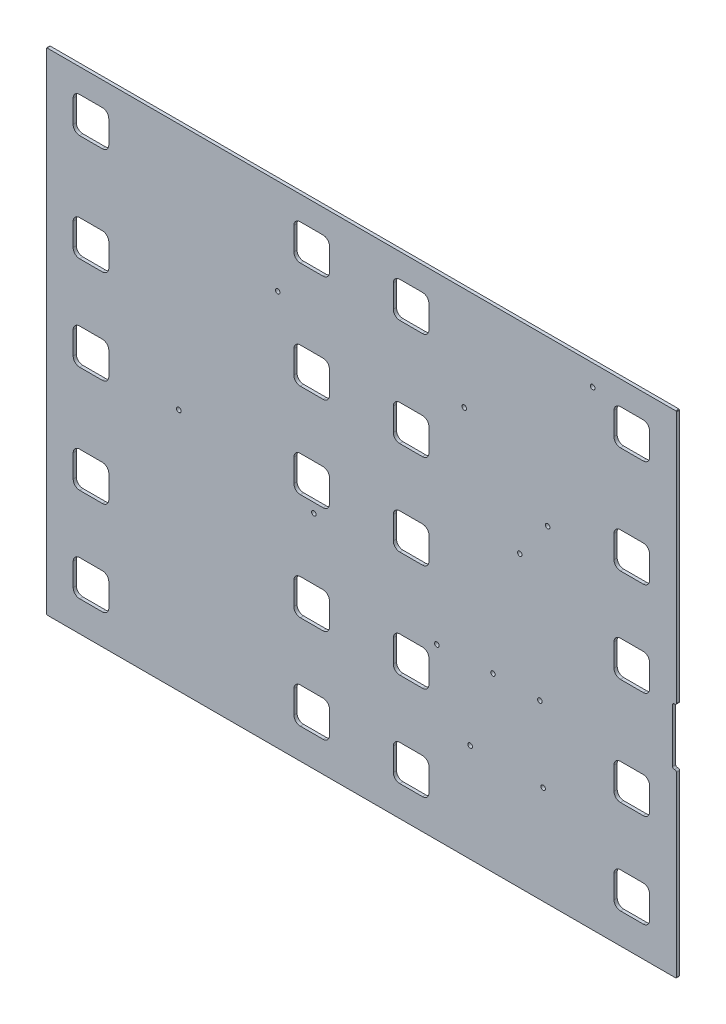
SolidWorks part; units mm, degrees
material "PP Film"
ref_plane "X-Y Datum" through (0, 0, 0) normal (0, 0, 1) x (1, 0, 0)
ref_plane "X-Z Datum" through (0, 0, 0) normal (0, 1, 0) x (1, 0, 0)
ref_plane "Y-Z Datum" through (0, 0, 0) normal (1, 0, 0) x (0, 0, -1)
sketch "Sketch9" plane through (0, 0, 0) normal (0, 0, 1) x (1, 0, 0)
  line L0 (-82.7559, -182.5893) -> (-82.7583, -160.1613) construction
  line L1 (-89.109, -153.8119) -> (-111.537, -153.8143) construction
  line L2 (-117.8863, -160.165) -> (-117.8839, -182.593) construction
  line L3 (-111.5333, -188.9423) -> (-89.1053, -188.9399) construction
  line L4 (476.4425, 172.8027) -> (-143.9348, 172.7375)
  line L12 (-111.5443, -83.8117) -> (-89.1163, -83.8093) construction
  line L13 (-82.767, -77.4587) -> (-82.7693, -55.0307) construction
  line L14 (-89.12, -48.6813) -> (-111.548, -48.6837) construction
  line L15 (-117.8973, -55.0344) -> (-117.895, -77.4624) construction
  line L16 (-82.7877, 120.2549) -> (-82.7901, 142.6829) construction
  line L17 (-89.1408, 149.0323) -> (-111.5688, 149.0299) construction
  line L18 (-117.9181, 142.6792) -> (-117.9157, 120.2512) construction
  line L19 (-111.5651, 113.9019) -> (-89.1371, 113.9043) construction
  line L20 (-111.554, 8.7713) -> (-89.126, 8.7737) construction
  line L21 (-117.9071, 37.5486) -> (-117.9047, 15.1206) construction
  line L22 (-89.1297, 43.9017) -> (-111.5577, 43.8993) construction
  line L23 (-82.7767, 15.1243) -> (-82.7791, 37.5523) construction
  line L24 (-82.7559, -182.5893) -> (-82.7583, -160.1613)
  line L25 (-89.109, -153.8119) -> (-111.537, -153.8143)
  line L26 (-117.8863, -160.165) -> (-117.8839, -182.593)
  line L27 (-111.5333, -188.9423) -> (-89.1053, -188.9399)
  line L28 (-111.5443, -83.8117) -> (-89.1163, -83.8093)
  line L29 (-82.767, -77.4587) -> (-82.7693, -55.0307)
  line L30 (-89.12, -48.6813) -> (-111.548, -48.6837)
  line L31 (-117.8973, -55.0344) -> (-117.895, -77.4624)
  line L32 (-82.7877, 120.2549) -> (-82.7901, 142.6829)
  line L33 (-89.1408, 149.0323) -> (-111.5688, 149.0299)
  line L34 (-117.9181, 142.6792) -> (-117.9157, 120.2512)
  line L35 (-111.5651, 113.9019) -> (-89.1371, 113.9043)
  line L36 (-111.554, 8.7713) -> (-89.126, 8.7737)
  line L37 (-117.9071, 37.5486) -> (-117.9047, 15.1206)
  line L38 (-89.1297, 43.9017) -> (-111.5577, 43.8993)
  line L39 (-82.7767, 15.1243) -> (-82.7791, 37.5523)
  line L40 (-82.7462, -275.1723) -> (-82.7486, -252.7443) construction
  line L41 (-89.0992, -246.3949) -> (-111.5272, -246.3973) construction
  line L42 (-117.8766, -252.748) -> (-117.8742, -275.176) construction
  line L43 (-111.5235, -281.5253) -> (-89.0955, -281.5229) construction
  line L44 (-82.7462, -275.1723) -> (-82.7486, -252.7443)
  line L45 (-89.0992, -246.3949) -> (-111.5272, -246.3973)
  line L46 (-117.8766, -252.748) -> (-117.8742, -275.176)
  line L47 (-111.5235, -281.5253) -> (-89.0955, -281.5229)
  line L195 (476.4425, 172.8027) -> (-143.9348, 172.7375)
  line L254 (-144.3754, 172.2968) -> (-144.3246, -311.0729)
  line L255 (-144.3754, 172.2968) -> (-144.3246, -311.0729)
  line L256 (-143.884, -311.5135) -> (476.4934, -311.4483)
  line L257 (-143.884, -311.5135) -> (476.4934, -311.4483)
  line L258 (476.934, -311.0077) -> (476.8832, 172.3621)
  line L259 (476.934, -311.0077) -> (476.8832, 172.3621)
  arc A0 (-89.1053, -188.9399) -> (-82.7559, -182.5893) centre (-89.1059, -182.5899) ccw construction
  arc A1 (-82.7583, -160.1613) -> (-89.109, -153.8119) centre (-89.1083, -160.1619) ccw construction
  arc A2 (-111.537, -153.8143) -> (-117.8863, -160.165) centre (-111.5363, -160.1643) ccw construction
  arc A3 (-117.8839, -182.593) -> (-111.5333, -188.9423) centre (-111.5339, -182.5923) ccw construction
  arc A4 (-89.1163, -83.8093) -> (-82.767, -77.4587) centre (-89.117, -77.4593) ccw construction
  arc A5 (-82.7693, -55.0307) -> (-89.12, -48.6813) centre (-89.1193, -55.0313) ccw construction
  arc A6 (-111.548, -48.6837) -> (-117.8973, -55.0344) centre (-111.5473, -55.0337) ccw construction
  arc A7 (-117.895, -77.4624) -> (-111.5443, -83.8117) centre (-111.545, -77.4617) ccw construction
  arc A8 (-89.1371, 113.9043) -> (-82.7877, 120.2549) centre (-89.1377, 120.2543) ccw construction
  arc A9 (-82.7901, 142.6829) -> (-89.1408, 149.0323) centre (-89.1401, 142.6823) ccw construction
  arc A10 (-111.5688, 149.0299) -> (-117.9181, 142.6792) centre (-111.5681, 142.6799) ccw construction
  arc A11 (-117.9157, 120.2512) -> (-111.5651, 113.9019) centre (-111.5657, 120.2519) ccw construction
  arc A12 (-82.7791, 37.5523) -> (-89.1297, 43.9017) centre (-89.1291, 37.5517) ccw construction
  arc A13 (-89.126, 8.7737) -> (-82.7767, 15.1243) centre (-89.1267, 15.1237) ccw construction
  arc A14 (-117.9047, 15.1206) -> (-111.554, 8.7713) centre (-111.5547, 15.1213) ccw construction
  arc A15 (-111.5577, 43.8993) -> (-117.9071, 37.5486) centre (-111.5571, 37.5493) ccw construction
  arc A16 (-89.1053, -188.9399) -> (-82.7559, -182.5893) centre (-89.1059, -182.5899) ccw
  arc A17 (-82.7583, -160.1613) -> (-89.109, -153.8119) centre (-89.1083, -160.1619) ccw
  arc A18 (-111.537, -153.8143) -> (-117.8863, -160.165) centre (-111.5363, -160.1643) ccw
  arc A19 (-117.8839, -182.593) -> (-111.5333, -188.9423) centre (-111.5339, -182.5923) ccw
  arc A20 (-89.1163, -83.8093) -> (-82.767, -77.4587) centre (-89.117, -77.4593) ccw
  arc A21 (-82.7693, -55.0307) -> (-89.12, -48.6813) centre (-89.1193, -55.0313) ccw
  arc A22 (-111.548, -48.6837) -> (-117.8973, -55.0344) centre (-111.5473, -55.0337) ccw
  arc A23 (-117.895, -77.4624) -> (-111.5443, -83.8117) centre (-111.545, -77.4617) ccw
  arc A24 (-89.1371, 113.9043) -> (-82.7877, 120.2549) centre (-89.1377, 120.2543) ccw
  arc A25 (-82.7901, 142.6829) -> (-89.1408, 149.0323) centre (-89.1401, 142.6823) ccw
  arc A26 (-111.5688, 149.0299) -> (-117.9181, 142.6792) centre (-111.5681, 142.6799) ccw
  arc A27 (-117.9157, 120.2512) -> (-111.5651, 113.9019) centre (-111.5657, 120.2519) ccw
  arc A28 (-82.7791, 37.5523) -> (-89.1297, 43.9017) centre (-89.1291, 37.5517) ccw
  arc A29 (-89.126, 8.7737) -> (-82.7767, 15.1243) centre (-89.1267, 15.1237) ccw
  arc A30 (-117.9047, 15.1206) -> (-111.554, 8.7713) centre (-111.5547, 15.1213) ccw
  arc A31 (-111.5577, 43.8993) -> (-117.9071, 37.5486) centre (-111.5571, 37.5493) ccw
  arc A32 (-89.0955, -281.5229) -> (-82.7462, -275.1723) centre (-89.0962, -275.1729) ccw construction
  arc A33 (-111.5272, -246.3973) -> (-117.8766, -252.748) centre (-111.5266, -252.7473) ccw construction
  arc A34 (-117.8742, -275.176) -> (-111.5235, -281.5253) centre (-111.5242, -275.1753) ccw construction
  arc A35 (-89.0955, -281.5229) -> (-82.7462, -275.1723) centre (-89.0962, -275.1729) ccw
  arc A36 (-111.5272, -246.3973) -> (-117.8766, -252.748) centre (-111.5266, -252.7473) ccw
  arc A37 (-117.8742, -275.176) -> (-111.5235, -281.5253) centre (-111.5242, -275.1753) ccw
  arc A38 (-82.7486, -252.7443) -> (-89.0992, -246.3949) centre (-89.0986, -252.7449) ccw construction
  arc A39 (-82.7486, -252.7443) -> (-89.0992, -246.3949) centre (-89.0986, -252.7449) ccw
  arc A72 (-143.884, -311.5135) -> (-144.3246, -311.0729) centre (-145.2049, -312.394) ccw
  arc A120 (-143.884, -311.5135) -> (-144.3246, -311.0729) centre (-145.2049, -312.394) ccw
  arc A150 (476.934, -311.0077) -> (476.4934, -311.4483) centre (477.8145, -312.3286) ccw
  arc A151 (476.934, -311.0077) -> (476.4934, -311.4483) centre (477.8145, -312.3286) ccw
  arc A152 (476.4425, 172.8027) -> (476.8832, 172.3621) centre (477.7634, 173.6832) ccw
  arc A153 (476.4425, 172.8027) -> (476.8832, 172.3621) centre (477.7634, 173.6832) ccw
  arc A154 (-144.3754, 172.2968) -> (-143.9348, 172.7375) centre (-145.2559, 173.6178) ccw
  arc A156 (-144.3754, 172.2968) -> (-143.9348, 172.7375) centre (-145.2559, 173.6178) ccw
  dimension "D1" = 0
extrude "Boss-Extrude2" add sketch "Sketch9" along normal blind 3.175 contours L255 L257 L195 A39 L44 A35 L47 A37 L46 A36 L45 A31 L38 A28 L39 A29 L36 A30 L37 A27 L34 A26 L33 A25 L32 A24 L35 A23 L31 A22 L30 A21 L29 A20 L28 A19 L26 A18 L25 A17 L24 A16 L27 | L44 A39 L45 A36 L46 A37 L47 A35 | L26 A19 L27 A16 L24 A17 L25 A18 | L38 A31 L37 A30 L36 A29 L39 A28 | L34 A27 L35 A24 L32 A25 L33 A26 | L31 A23 L28 A20 L29 A21 L30 A22 region at (171.7018, -69.3676, 0) region at (-100.3211, -171.3771, 0) region at (-100.3322, -66.2465, 0) region at (-100.3529, 131.4671, 0) region at (-100.3419, 26.3365, 0) region at (-100.3114, -263.9601, 0)
sketch "Sketch10" plane through (0, 0, 3.175) normal (0, 0, 1) x (1, 0, 0)
  line L9 (476.8831, 172.8027) -> (-144.3755, 172.7375)
  line L10 (-144.3755, 172.7375) -> (-144.3246, -311.5135)
  line L11 (-144.3246, -311.5135) -> (476.934, -311.4483)
  line L12 (-117.8863, -160.165) -> (-117.8839, -182.593)
  line L13 (-111.5333, -188.9423) -> (-89.1053, -188.9399)
  line L14 (-82.7559, -182.5893) -> (-82.7583, -160.1613)
  line L15 (-89.109, -153.8119) -> (-111.537, -153.8143)
  line L16 (-117.8863, -160.165) -> (-117.8839, -182.593)
  line L17 (-111.5333, -188.9423) -> (-89.1053, -188.9399)
  line L18 (-82.7559, -182.5893) -> (-82.7583, -160.1613)
  line L19 (-89.109, -153.8119) -> (-111.537, -153.8143)
  line L20 (-117.8766, -252.748) -> (-117.8742, -275.176)
  line L21 (-89.0992, -246.3949) -> (-111.5272, -246.3973)
  line L22 (-82.7462, -275.1723) -> (-82.7486, -252.7443)
  line L23 (-111.5235, -281.5253) -> (-89.0955, -281.5229)
  line L24 (-117.8766, -252.748) -> (-117.8742, -275.176)
  line L25 (-89.0992, -246.3949) -> (-111.5272, -246.3973)
  line L26 (-82.7462, -275.1723) -> (-82.7486, -252.7443)
  line L27 (-111.5235, -281.5253) -> (-89.0955, -281.5229)
  line L28 (-89.12, -48.6813) -> (-111.548, -48.6837)
  line L29 (-117.8973, -55.0344) -> (-117.895, -77.4624)
  line L30 (-111.5443, -83.8117) -> (-89.1163, -83.8093)
  line L31 (-82.767, -77.4587) -> (-82.7693, -55.0307)
  line L32 (-89.12, -48.6813) -> (-111.548, -48.6837)
  line L33 (-117.8973, -55.0344) -> (-117.895, -77.4624)
  line L34 (-111.5443, -83.8117) -> (-89.1163, -83.8093)
  line L35 (-82.767, -77.4587) -> (-82.7693, -55.0307)
  line L36 (-82.7877, 120.2549) -> (-82.7901, 142.6829)
  line L37 (-111.5651, 113.9019) -> (-89.1371, 113.9043)
  line L38 (-117.9181, 142.6792) -> (-117.9157, 120.2512)
  line L39 (-89.1408, 149.0323) -> (-111.5688, 149.0299)
  line L40 (-82.7877, 120.2549) -> (-82.7901, 142.6829)
  line L41 (-111.5651, 113.9019) -> (-89.1371, 113.9043)
  line L42 (-117.9181, 142.6792) -> (-117.9157, 120.2512)
  line L43 (-89.1408, 149.0323) -> (-111.5688, 149.0299)
  line L44 (-111.554, 8.7713) -> (-89.126, 8.7737)
  line L45 (-82.7767, 15.1243) -> (-82.7791, 37.5523)
  line L46 (-89.1297, 43.9017) -> (-111.5577, 43.8993)
  line L47 (-117.9071, 37.5486) -> (-117.9047, 15.1206)
  line L48 (-111.554, 8.7713) -> (-89.126, 8.7737)
  line L49 (-82.7767, 15.1243) -> (-82.7791, 37.5523)
  line L50 (-89.1297, 43.9017) -> (-111.5577, 43.8993)
  line L51 (-117.9071, 37.5486) -> (-117.9047, 15.1206)
  line L53 (476.934, -311.4483) -> (476.8831, 172.8027)
  arc A4 (-117.8839, -182.593) -> (-111.5333, -188.9423) centre (-111.5339, -182.5923) ccw
  arc A5 (-89.1053, -188.9399) -> (-82.7559, -182.5893) centre (-89.1059, -182.5899) ccw
  arc A6 (-82.7583, -160.1613) -> (-89.109, -153.8119) centre (-89.1083, -160.1619) ccw
  arc A7 (-111.537, -153.8143) -> (-117.8863, -160.165) centre (-111.5363, -160.1643) ccw
  arc A8 (-117.8839, -182.593) -> (-111.5333, -188.9423) centre (-111.5339, -182.5923) ccw
  arc A9 (-89.1053, -188.9399) -> (-82.7559, -182.5893) centre (-89.1059, -182.5899) ccw
  arc A10 (-82.7583, -160.1613) -> (-89.109, -153.8119) centre (-89.1083, -160.1619) ccw
  arc A11 (-111.537, -153.8143) -> (-117.8863, -160.165) centre (-111.5363, -160.1643) ccw
  arc A12 (-111.5272, -246.3973) -> (-117.8766, -252.748) centre (-111.5266, -252.7473) ccw
  arc A13 (-82.7486, -252.7443) -> (-89.0992, -246.3949) centre (-89.0986, -252.7449) ccw
  arc A14 (-89.0955, -281.5229) -> (-82.7462, -275.1723) centre (-89.0962, -275.1729) ccw
  arc A15 (-117.8742, -275.176) -> (-111.5235, -281.5253) centre (-111.5242, -275.1753) ccw
  arc A16 (-111.5272, -246.3973) -> (-117.8766, -252.748) centre (-111.5266, -252.7473) ccw
  arc A17 (-82.7486, -252.7443) -> (-89.0992, -246.3949) centre (-89.0986, -252.7449) ccw
  arc A18 (-89.0955, -281.5229) -> (-82.7462, -275.1723) centre (-89.0962, -275.1729) ccw
  arc A19 (-117.8742, -275.176) -> (-111.5235, -281.5253) centre (-111.5242, -275.1753) ccw
  arc A20 (-111.548, -48.6837) -> (-117.8973, -55.0344) centre (-111.5473, -55.0337) ccw
  arc A21 (-117.895, -77.4624) -> (-111.5443, -83.8117) centre (-111.545, -77.4617) ccw
  arc A22 (-89.1163, -83.8093) -> (-82.767, -77.4587) centre (-89.117, -77.4593) ccw
  arc A23 (-82.7693, -55.0307) -> (-89.12, -48.6813) centre (-89.1193, -55.0313) ccw
  arc A24 (-111.548, -48.6837) -> (-117.8973, -55.0344) centre (-111.5473, -55.0337) ccw
  arc A25 (-117.895, -77.4624) -> (-111.5443, -83.8117) centre (-111.545, -77.4617) ccw
  arc A26 (-89.1163, -83.8093) -> (-82.767, -77.4587) centre (-89.117, -77.4593) ccw
  arc A27 (-82.7693, -55.0307) -> (-89.12, -48.6813) centre (-89.1193, -55.0313) ccw
  arc A28 (-89.1371, 113.9043) -> (-82.7877, 120.2549) centre (-89.1377, 120.2543) ccw
  arc A29 (-117.9157, 120.2512) -> (-111.5651, 113.9019) centre (-111.5657, 120.2519) ccw
  arc A30 (-111.5688, 149.0299) -> (-117.9181, 142.6792) centre (-111.5681, 142.6799) ccw
  arc A31 (-82.7901, 142.6829) -> (-89.1408, 149.0323) centre (-89.1401, 142.6823) ccw
  arc A32 (-89.1371, 113.9043) -> (-82.7877, 120.2549) centre (-89.1377, 120.2543) ccw
  arc A33 (-117.9157, 120.2512) -> (-111.5651, 113.9019) centre (-111.5657, 120.2519) ccw
  arc A34 (-111.5688, 149.0299) -> (-117.9181, 142.6792) centre (-111.5681, 142.6799) ccw
  arc A35 (-82.7901, 142.6829) -> (-89.1408, 149.0323) centre (-89.1401, 142.6823) ccw
  arc A36 (-89.126, 8.7737) -> (-82.7767, 15.1243) centre (-89.1267, 15.1237) ccw
  arc A37 (-82.7791, 37.5523) -> (-89.1297, 43.9017) centre (-89.1291, 37.5517) ccw
  arc A38 (-111.5577, 43.8993) -> (-117.9071, 37.5486) centre (-111.5571, 37.5493) ccw
  arc A39 (-117.9047, 15.1206) -> (-111.554, 8.7713) centre (-111.5547, 15.1213) ccw
  arc A40 (-89.126, 8.7737) -> (-82.7767, 15.1243) centre (-89.1267, 15.1237) ccw
  arc A41 (-82.7791, 37.5523) -> (-89.1297, 43.9017) centre (-89.1291, 37.5517) ccw
  arc A42 (-111.5577, 43.8993) -> (-117.9071, 37.5486) centre (-111.5571, 37.5493) ccw
  arc A43 (-117.9047, 15.1206) -> (-111.554, 8.7713) centre (-111.5547, 15.1213) ccw
  dimension "D2" = 0
  dimension "D3" = 0
  dimension "D4" = 0
  dimension "D5" = 0
  dimension "D6" = 0
extrude "Cut-Extrude6" cut sketch "Sketch10" against normal through all contours L40 A35 L43 A34 L42 A33 L41 A32 | L51 A43 L48 A40 L49 A41 L50 A42 | L35 A27 L32 A24 L33 A25 L34 A26 | L19 A11 L16 A8 L17 A9 L18 A10 | L24 A19 L27 A18 L26 A17 L25 A16 region at (-100.3211, -171.3771, 3.175) region at (-100.3114, -263.9601, 3.175) region at (-100.3322, -66.2465, 3.175) region at (-100.3529, 131.4671, 3.175) region at (-100.3419, 26.3365, 3.175)
pattern_linear "LPattern2" count 2 spacing 217.5764 along (1, 0.0001, 0) of "Cut-Extrude6"
ref_plane "Plane1" through (166.272, 0.0175, 0) normal (-1, -0.0001, 0) x (0, 0, 1)
mirror "Mirror1" about plane through (166.272, 0.0175, 0) normal (-1, -0.0001, 0) of "LPattern2", "Cut-Extrude6"
sketch "Sketch11" plane through (0, 0, 3.175) normal (0, 0, 1) x (1, 0, 0)
  circle A3 centre (296.0387, -141.6048) radius 1.5875
  circle A5 centre (296.0387, -141.6048) radius 1.5875
  circle A7 centre (394.3353, 152.1565) radius 1.5875
  circle A9 centre (394.3353, 152.1565) radius 1.5875
  circle A11 centre (267.6913, 71.3582) radius 1.5875
  circle A13 centre (267.6913, 71.3582) radius 1.5875
  circle A15 centre (83.7969, 78.6239) radius 1.5875
  circle A17 centre (83.7969, 78.6239) radius 1.5875
  circle A19 centre (-13.7373, -71.3863) radius 1.5875
  circle A21 centre (-13.7373, -71.3863) radius 1.5875
  circle A23 centre (349.9236, 11.0749) radius 1.5875
  circle A44 centre (349.9236, 11.0749) radius 1.5875
  circle A45 centre (322.4275, -26.052) radius 1.5875
  circle A46 centre (322.4275, -26.052) radius 1.5875
  circle A47 centre (342.2387, -141.5999) radius 1.5875
  circle A48 centre (342.2387, -141.5999) radius 1.5875
  circle A49 centre (345.5113, -214.3496) radius 1.5875
  circle A50 centre (345.5113, -214.3496) radius 1.5875
  circle A51 centre (119.4061, -93.0712) radius 1.5875
  circle A52 centre (119.4061, -93.0712) radius 1.5875
  circle A53 centre (240.6965, -144.4935) radius 1.5875
  circle A54 centre (240.6965, -144.4935) radius 1.5875
  circle A55 centre (273.5113, -214.3572) radius 1.5875
  circle A56 centre (273.5113, -214.3572) radius 1.5875
  dimension "D1" = 0
  dimension "D2" = 0
  dimension "D3" = 0
  dimension "D4" = 0
  dimension "D5" = 0
  dimension "D6" = 0
  dimension "D7" = 0
  dimension "D8" = 0
  dimension "D9" = 0
  dimension "D10" = 0
  dimension "D11" = 0
  dimension "D12" = 0
sketch "Sketch12" plane through (0, 0, 3.175) normal (0, 0, 1) x (1, 0, 0)
  line L0 (472.9633, -129.0942) -> (472.9585, -83.0942)
  line L1 (472.9632, -127.919) -> (472.9635, -130.2694) construction
  line L2 (472.9584, -81.919) -> (472.9586, -84.2694) construction
  line L3 (476.934, -311.0077) -> (476.8832, 172.3621) construction
  line L4 (472.9609, -78.1542) -> (472.9609, -134.0342)
  line L5 (472.9609, -134.0342) -> (476.9154, -134.0342)
  line L6 (472.9609, -78.1542) -> (476.9095, -78.1542)
  line L9 (476.934, -311.0077) -> (476.8832, 172.3621)
  point P11 (472.9609, -106.0942)
  dimension "D1" = 46
  dimension "D2" = 55.88
extrude "Cut-Extrude8" cut sketch "Sketch12" against normal through all contours L9 region at (474.9367, -106.1011, 3.175)
fillet "Fillet1" radius 1.5875 4 edges at (472.9609, -78.1542, 1.5875) (472.9609, -134.0342, 1.5875) (476.9095, -78.1542, 1.5875) (476.9154, -134.0342, 1.5875)
hole_wizard "M4 Clearance Hole1" positions "Sketch13" profile "Sketch14" hole size "M4" standard "ANSI Metric" end condition through all
sketch "Sketch13" plane through (0, 0, 3.175) normal (0, 0, 1) x (1, 0, 0)
  point P0 (-13.7373, -71.3863)
  point P3 (119.4061, -93.0712)
  point P6 (273.5113, -214.3572)
  point P9 (345.5113, -214.3496)
  point P12 (240.6965, -144.4935)
  point P15 (296.0387, -141.6048)
  point P18 (342.2387, -141.5999)
  point P21 (322.4275, -26.052)
  point P24 (349.9236, 11.0749)
  point P27 (267.6913, 71.3582)
  point P30 (394.3353, 152.1565)
  point P33 (83.7969, 78.6239)
sketch "Sketch14" plane through (-13.7373, -71.3863, 3.175) normal (1, 0, 0) x (0, -1, 0)
  line L0 (0, 0) -> (0, 3.175)
  line L1 (0, 3.175) -> (2.25, 3.175)
  line L2 (2.25, 3.175) -> (2.25, 0)
  line L5 (2.25, 0) -> (0, 0)
  line L11 (0, -6.35) -> (0, 107.95) construction
  dimension "Thru Hole Dia." = 4.5
  dimension "Thru Hole Depth" = 3.175
fillet "Fillet2" radius 0.7937 8 edges at (-143.884, -311.5135, 1.5875) (-144.3246, -311.0729, 1.5875) (476.4934, -311.4483, 1.5875) (476.934, -311.0077, 1.5875) (476.8832, 172.3621, 1.5875) (476.4425, 172.8027, 1.5875) (-143.9348, 172.7375, 1.5875) (-144.3754, 172.2968, 1.5875)
